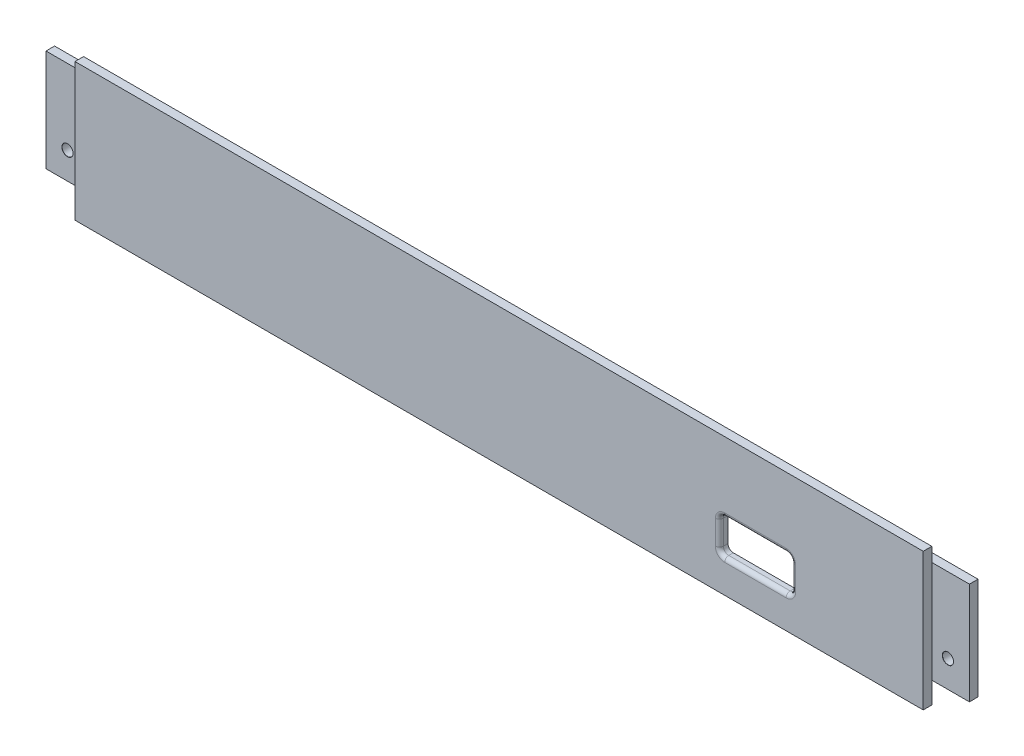
SolidWorks part; units mm, degrees
ref_plane "Front Plane" through (0, 0, 0) normal (0, 0, 1) x (1, 0, 0)
ref_plane "Top Plane" through (0, 0, 0) normal (0, 1, 0) x (1, 0, 0)
ref_plane "Right Plane" through (0, 0, 0) normal (1, 0, 0) x (0, 0, -1)
sketch "Sketch1" plane through (0, 0, 0) normal (0, 0, 1) x (1, 0, 0)
  line L0 (0, -55) -> (0, 55) construction
  line L1 (-79, 25.6) -> (79, 25.6)
  line L2 (-79, 25.6) -> (-79, 0)
  line L3 (-79, 0) -> (79, 0)
  line L4 (79, 25.6) -> (79, 0)
  line L5 (55, 0) -> (-55, 0) construction
  dimension "D1" = 158
  dimension "D2" = 25.6
  dimension "D3" = 79
  dimension "D4" = 0
extrude "Primary backplate" add sketch "Sketch1" along normal blind 1.6
sketch "Sketch2" plane through (0, 0, 0) normal (0, 0, 1) x (1, 0, 0)
  line L0 (-79, 0) -> (79, 0) construction
  line L1 (-86, 23) -> (86, 23)
  line L2 (-86, 23) -> (-86, 4)
  line L3 (-86, 4) -> (86, 4)
  line L4 (86, 23) -> (86, 4)
  line L5 (0, 26.3642) -> (0, -16.9121) construction
  line L6 (-79, 25.6) -> (-79, 0) construction
  dimension "D1" = 172
  dimension "D2" = 19
  dimension "D3" = 4
  dimension "D4" = 79
  dimension "D5" = 86
extrude "Plate thickener" add sketch "Sketch2" against normal blind 1.6
hole_wizard "Tap Drill for M2.5x0.45 Tap3" positions "3DSketch3" profile "Sketch5" hole size "M2.5x0.45" standard "ANSI Metric" end condition through all
sketch3d "3DSketch3"
  point P0 (-82, 9, 0)
  point P3 (82, 9, 0)
  dimension "D1" = 82
  dimension "D2" = 82
  dimension "D3" = 9
  dimension "D4" = 9
sketch "Sketch5" plane through (-82, 9, 0) normal (1, 0, 0) x (0, -1, 0)
  line L0 (0, 0) -> (0, 1.6)
  line L1 (0, 1.6) -> (1.025, 1.6)
  line L2 (1.025, 1.6) -> (1.025, 0.025)
  line L3 (1.025, 0.025) -> (1.05, 0)
  line L5 (1.05, 0) -> (0, 0)
  line L6 (-1.025, 0.025) -> (-1.05, 0) construction
  line L11 (0, -6.35) -> (0, 107.95) construction
  dimension "Thru Hole Dia." = 2.05
  dimension "Thru Hole Depth" = 1.6
  dimension "Near C'Sink Dia." = 2.1
  dimension "Near C'Sink Angle" = 90
ref_plane "PCB top" through (0, 1.6, 0) normal (0, 1, 0) x (1, 0, 0)
sketch "Sketch7" plane through (0, 1.6, 0) normal (0, 1, 0) x (1, 0, 0)
  line L0 (0, -1.76) -> (0, 1.76) construction
  line L1 (-80.9, 68.51) -> (80.9, 68.51) construction
  line L2 (-80.9, 68.51) -> (-80.9, 0.51) construction
  line L3 (-80.9, 0.51) -> (80.9, 0.51) construction
  line L4 (80.9, 68.51) -> (80.9, 0.51) construction
  line L5 (-14.08, 0) -> (14.08, 0) construction
  line L6 (-60.9, 68.51) -> (-60.9, 0) construction
  line L7 (70.9, 68.51) -> (70.9, 0) construction
  line L9 (-60.9, 0) -> (-52.9, 0)
  line L10 (-60.9, 0) -> (-60.9, 7)
  line L11 (-60.9, 7) -> (-52.9, 7)
  line L12 (-52.9, 0) -> (-52.9, 7)
  line L13 (70.9, 0) -> (62.9, 0)
  line L14 (70.9, 0) -> (70.9, 7)
  line L15 (70.9, 7) -> (62.9, 7)
  line L16 (62.9, 0) -> (62.9, 7)
  circle A0 centre (-56.9, 4.51) radius 1.3
  circle A1 centre (66.9, 4.51) radius 1.3
  dimension "D14" = 2.6
  dimension "D15" = 2.6
  dimension "D1" = 80.9
  dimension "D2" = 80.9
  dimension "D3" = 0.51
  dimension "D4" = 68
  dimension "D5" = 20
  dimension "D6" = 10
  dimension "8" = 8
  dimension "D8" = 7
  dimension "D9" = 8
  dimension "D10" = 7
  dimension "D11" = 4
  dimension "D7" = 4
  dimension "D12" = 4
  dimension "D13" = 4
extrude "Mounting bosses" add sketch "Sketch7" along normal blind 4 separate body
sketch "Sketch8" plane through (0, 0, 0) normal (0, 0, 1) x (1, 0, 0)
  line L1 (54.4613, 12.5653) -> (41.0239, 12.5653)
  line L2 (54.4613, 12.5653) -> (54.4613, 6.0644)
  line L3 (54.4613, 6.0644) -> (41.0239, 6.0644)
  line L4 (41.0239, 12.5653) -> (41.0239, 6.0644)
extrude "USB hole" cut sketch "Sketch8" against normal through all both and the other way through all
combine bodies "Combine1" operation type add bodies to combine 108 107 106
fillet "Fillet1" radius 0.5 6 edges at (-52.9, 4.8, -1.6) (-60.9, 4.8, -1.6) (-56.9, 5.6, -1.6) (70.9, 4.8, -1.6) (62.9, 4.8, -1.6) (66.9, 5.6, -1.6)
sketch "Sketch9" plane through (0, 0, -1.6) normal (0, 0, -1) x (-1, 0, 0)
  line L1 (-61.6916, 16.2443) -> (-32.4345, 16.2443)
  line L2 (-61.6916, 16.2443) -> (-61.6916, 0.4655)
  line L3 (-61.6916, 0.4655) -> (-32.4345, 0.4655)
  line L4 (-32.4345, 16.2443) -> (-32.4345, 0.4655)
extrude "module relief" cut sketch "Sketch9" against normal up to surface (1.6 mm away) up to face at (0, 24.3, 0)
fillet "Fillet2" radius 1 4 edges at (41.0239, 6.0644, 0.8) (54.4613, 6.0644, 0.8) (54.4613, 12.5653, 0.8) (41.0239, 12.5653, 0.8)
fillet "Fillet3" radius 0.75 8 edges at (41.3168, 12.2724, 1.6) (47.7426, 12.5653, 1.6) (54.1684, 12.2724, 1.6) (54.4613, 9.3148, 1.6) (54.1684, 6.3573, 1.6) (47.7426, 6.0644, 1.6) (41.3168, 6.3573, 1.6) (41.0239, 9.3148, 1.6)
sketch "Sketch12" plane through (0, 0, -1.6) normal (0, 0, -1) x (-1, 0, 0)
  line L1 (-24.2469, 3.8271) -> (-20.6338, 3.8271)
  line L2 (-24.2469, 3.8271) -> (-24.2469, 1.9254)
  line L3 (-24.2469, 1.9254) -> (-20.6338, 1.9254)
  line L4 (-20.6338, 3.8271) -> (-20.6338, 1.9254)
extrude "LED hole" cut sketch "Sketch12" against normal offset from surface (3 mm away) 0.2 up to face at (47.7426, 9.3148, 1.6)
equation "\"D4@Sketch2\"=158/2"
equation "\"D5@Sketch2\"=172/2"
equation "\"D3@Sketch1\"=158/2"
equation "\"D1\"= 164 / 2"
equation "\"D1@3DSketch3\"=164/2"
equation "\"D2@3DSketch3\"=164/2"
equation "\"D1@Sketch7\"=161.8/2"
equation "\"D2@Sketch7\"=\"D1@Sketch7\""
equation "\"D9@Sketch7\"=\"8@Sketch7\""
equation "\"D10@Sketch7\"=\"D8@Sketch7\""
equation "\"D7@Sketch7\"=\"D11@Sketch7\""
equation "\"D15@Sketch7\"=\"D14@Sketch7\""
equation "\"D13@Sketch7\"=\"D12@Sketch7\""
